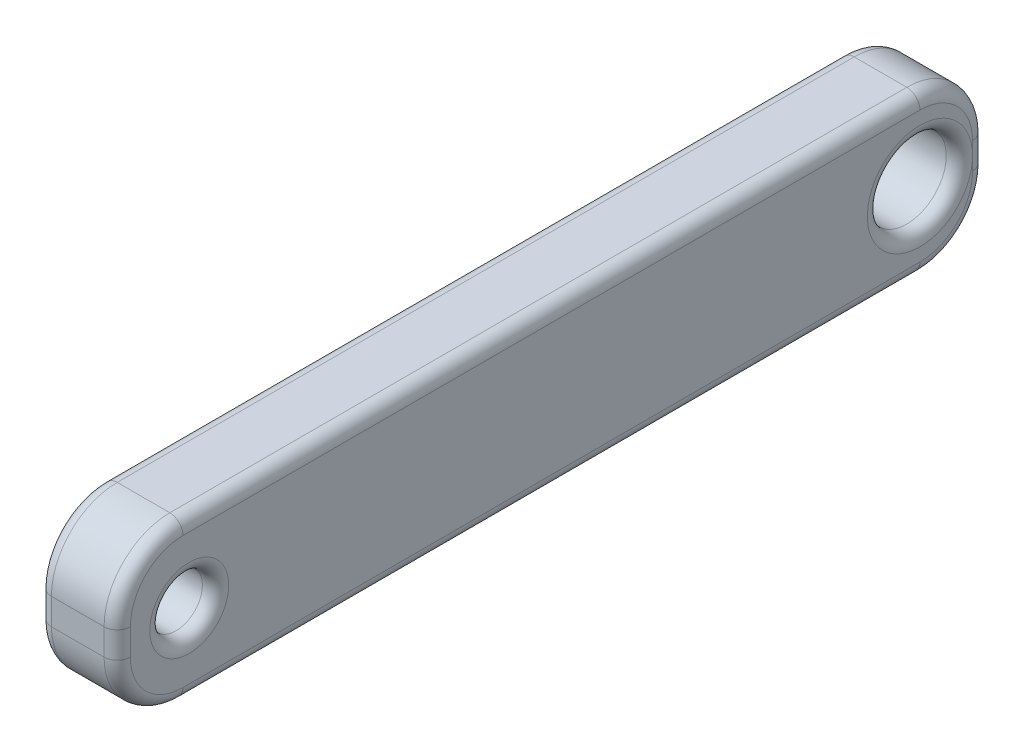
SolidWorks part; units mm, degrees
ref_plane "Front Plane" through (0, 0, 0) normal (0, 0, 1) x (1, 0, 0)
ref_plane "Top Plane" through (0, 0, 0) normal (0, 1, 0) x (1, 0, 0)
ref_plane "Right Plane" through (0, 0, 0) normal (1, 0, 0) x (0, 0, -1)
sketch "Sketch1" plane through (0, 0, 0) normal (1, 0, 0) x (0, 0, -1)
  line L1 (2.5, 0) -> (30.5, 0)
  line L2 (0, 2.5) -> (0, 3.5)
  line L3 (2.5, 6) -> (30.5, 6)
  line L4 (33, 2.5) -> (33, 3.5)
  circle A0 centre (2.7359, 3) radius 1
  arc A2 (33, 3.5) -> (30.5, 6) centre (30.5, 3.5) ccw
  arc A3 (33, 2.5) -> (30.5, 0) centre (30.5, 2.5) cw
  arc A4 (0, 2.5) -> (2.5, 0) centre (2.5, 2.5) ccw
  arc A5 (0, 3.5) -> (2.5, 6) centre (2.5, 3.5) cw
  point P11 (33, 6)
  point P16 (0, 0)
  point P19 (0, 6)
  dimension "D3" = 2
  dimension "D4" = 2.5
  dimension "D1" = 33
  dimension "D2" = 6
extrude "Boss-Extrude1" add sketch "Sketch1" along normal blind 3
sketch "Sketch2" plane through (0, 0, 0) normal (-1, 0, 0) x (0, 0, 1)
  line L0 (-33, 3) -> (0, 3) construction
  line L1 (-33, 2.5) -> (-33, 3.5) construction
  line L2 (0, 3.5) -> (0, 2.5) construction
  circle A0 centre (-30.5, 3) radius 1.5
  dimension "D1" = 3
  dimension "D2" = 2.5
extrude "Cut-Extrude1" cut sketch "Sketch2" against normal blind 10
fillet "Fillet1" radius 0.5 20 edges at (0, 3, -3.7359) (0, 6, -16.5) (0, 5.2678, -0.7322) (0, 3, 0) (0, 0.7322, -0.7322) (0, 0, -16.5) (0, 0.7322, -32.2678) (0, 3, -33) (0, 5.2678, -32.2678) (0, 3, -29) (3, 3, -3.7359) (3, 3, -33) (3, 0.7322, -32.2678) (3, 0, -16.5) (3, 0.7322, -0.7322) (3, 3, 0) (3, 5.2678, -0.7322) (3, 6, -16.5) (3, 5.2678, -32.2678) (3, 3, -32)
